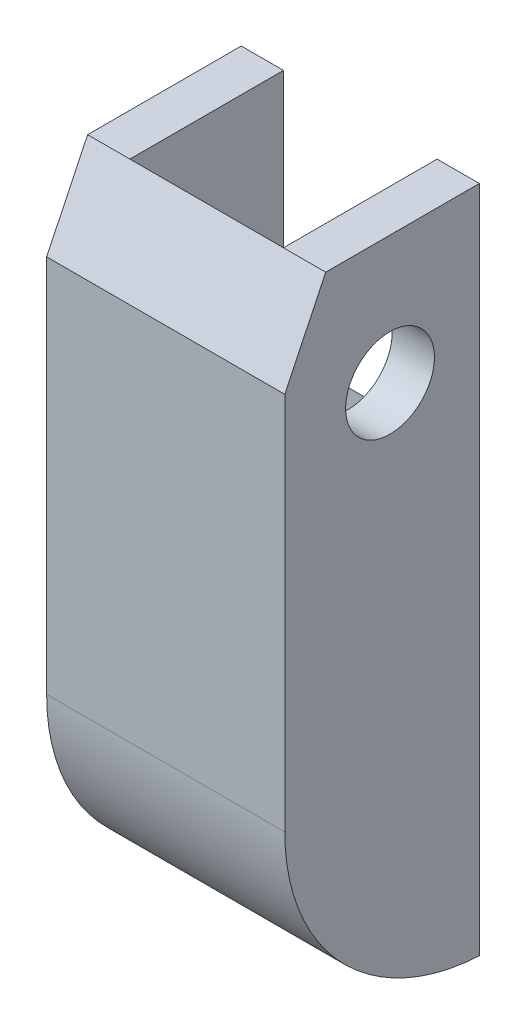
SolidWorks part; units mm, degrees
ref_plane "Front Plane" through (0, 0, 0) normal (0, 0, 1) x (1, 0, 0)
ref_plane "Top Plane" through (0, 0, 0) normal (0, 1, 0) x (1, 0, 0)
ref_plane "Right Plane" through (0, 0, 0) normal (1, 0, 0) x (0, 0, -1)
sketch "Sketch1" plane through (0, 0, 0) normal (0, 0, 1) x (1, 0, 0)
  line L1 (0, 0) -> (11.811, 0)
  line L2 (0, 0) -> (0, 45.9892)
  line L3 (0, 45.9892) -> (11.811, 45.9892)
  line L4 (11.811, 0) -> (11.811, 45.9892)
  dimension "D1" = 11.811
  dimension "D2" = 45.9892
extrude "Boss-Extrude1" add sketch "Sketch1" along normal blind 9.652 contours L2 L3 L4 L1
fillet "Fillet5" radius 4.826 1 edges at (5.9055, 45.9892, 0)
sketch "Sketch2" plane through (0, 0, 0) normal (0, 0, -1) x (-1, 0, 0)
  line L0 (0, 45.9892) -> (-11.811, 45.9892) construction
  line L1 (-9.7155, 45.9892) -> (-2.0955, 45.9892)
  line L2 (-9.7155, 45.9892) -> (-9.7155, 23.6372)
  line L3 (-9.7155, 23.6372) -> (-2.0955, 23.6372)
  line L4 (-2.0955, 45.9892) -> (-2.0955, 23.6372)
  line L5 (0, 0) -> (0, 41.1632) construction
  dimension "D1" = 22.352
  dimension "D2" = 7.62
  dimension "D3" = 2.0955
extrude "Cut-Extrude1" cut sketch "Sketch2" against normal blind 7.62
sketch "Sketch3" plane through (0, 0, 0) normal (-1, 0, 0) x (0, 0, 1)
  line L0 (7.62, 45.9892) -> (7.62, 23.6372) construction
  line L2 (7.62, 23.6372) -> (0, 23.6372) construction
  circle A0 centre (4.4323, 26.8249) radius 2.2035
  dimension "D1" = 3.1877
  dimension "D3" = 4.4069
  dimension "D2" = 3.1877
extrude "Cut-Extrude2" cut sketch "Sketch3" against normal through all and the other way through all
fillet "Fillet4" radius 4.826 1 edges at (5.9055, 45.9892, 9.652)
fillet "Fillet6" radius 10.16 1 edges at (5.9055, 0, 9.652)
sketch "Sketch4" plane through (11.811, 0, 0) normal (1, 0, 0) x (0, 0, -1)
  line L0 (-9.652, 28.9438) -> (-7.62, 33.1749)
  line L1 (-9.652, 10.1473) -> (-9.652, 41.1632) construction
  line L2 (-7.62, 33.1749) -> (0, 33.1749)
  line L3 (0, 0) -> (0, 41.1632) construction
  line L4 (-9.652, 28.9438) -> (-9.652, 45.9892)
  line L5 (-9.652, 45.9892) -> (0, 45.9892)
  line L6 (0, 45.9892) -> (0, 33.1749)
  line L7 (-0.4369, 28.7437) -> (4.2626, 18.9582) construction
  line L8 (-4.4323, 26.8249) -> (0, 26.8249) construction
  line L9 (-4.4323, 26.8249) -> (-0.4369, 28.7437) construction
  line L10 (-4.4323, 26.8249) -> (-0.4369, 24.9061) construction
  arc A0 (-4.826, 45.9892) -> (-9.652, 41.1632) centre (-4.826, 41.1632) ccw construction
  circle A1 centre (7.1247, 20.3327) radius 3.175 construction
  point P14 (-4.4323, 26.8249)
  point P22 (0, 0)
  point P23 (0, 0)
  dimension "D2" = 6.35
  dimension "D1" = 6.35
  dimension "D3" = 11.557
  dimension "D4" = 6.4922
extrude "Cut-Extrude3" cut sketch "Sketch4" against normal through all
sketch "Sketch5" plane through (9.7155, 0, 0) normal (-1, 0, 0) x (0, 0, 1)
  line L0 (5.1581, 23.6372) -> (0, 21.1601)
  line L1 (0, 21.1601) -> (0, 23.6372)
  line L2 (0, 23.6372) -> (5.1581, 23.6372)
  line L3 (4.4323, 26.8249) -> (0.4369, 24.9061) construction
  line L4 (4.4323, 26.8249) -> (7.62, 26.8249) construction
  line L5 (4.4323, 26.8249) -> (5.8123, 23.9514) construction
  line L6 (7.62, 33.1749) -> (7.62, 23.6372) construction
  line L7 (5.8123, 23.9514) -> (5.1581, 23.6372)
  line L8 (7.62, 26.8249) -> (7.62, 23.6372)
  line L9 (7.62, 23.6372) -> (5.1581, 23.6372)
  arc A0 (5.8123, 23.9514) -> (7.62, 26.8249) centre (4.4323, 26.8249) ccw
  point P2 (7.62, 26.845)
  point P13 (0, 0)
  line M4 (7.62, 23.6372) -> (7.62, 33.1749)
  line M7 (0, 23.6372) -> (7.62, 23.6372)
extrude "Cut-Extrude4" cut sketch "Sketch5" along normal up to surface (7.62 mm away) contours L1 L0 M7 region at (9.7155, 22.8115, 1.7194) up to face at (2.0955, 24.6215, 4.4323)
extrude "Boss-Extrude2" add sketch "Sketch5<3>" along normal up to surface (7.62 mm away) contours A0 L7 M7 M4 region at (9.7155, 24.361, 6.9399) up to face at (2.0955, 24.6215, 4.4323)
sketch "Sketch5<3>" plane through (9.7155, 0, 0) normal (-1, 0, 0) x (0, 0, 1) same geometry as "Sketch5"
